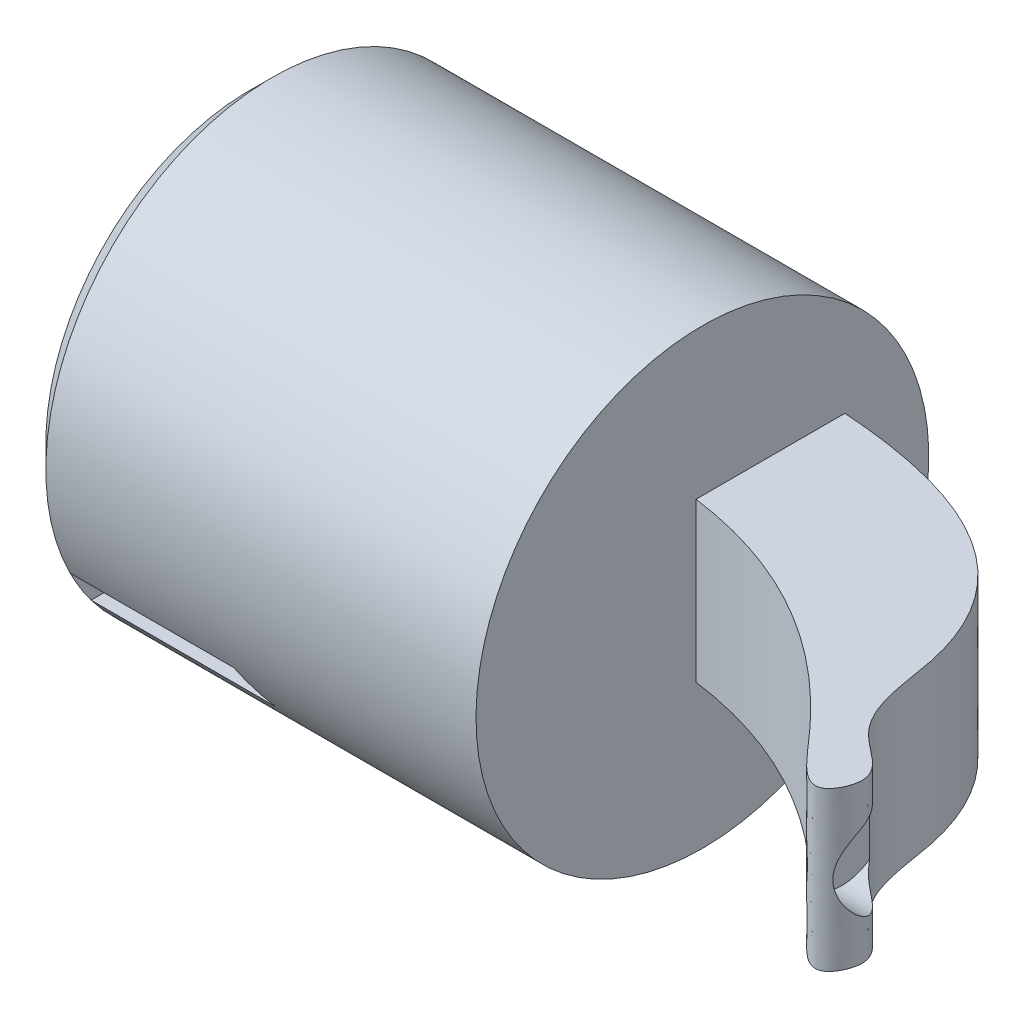
SolidWorks part; units mm, degrees
ref_plane "Front Plane" through (0, 0, 0) normal (0, 0, 1) x (1, 0, 0)
ref_plane "Top Plane" through (0, 0, 0) normal (0, 1, 0) x (1, 0, 0)
ref_plane "Right Plane" through (0, 0, 0) normal (1, 0, 0) x (0, 0, -1)
sketch "Sketch1" plane through (0, 0, 0) normal (1, 0, 0) x (0, 0, -1)
  circle A0 centre (0, 0) radius 10
  dimension "D1" = 20
extrude "Boss-Extrude1" add sketch "Sketch1" against normal blind 20
sketch "Sketch2" plane through (0, 0, 0) normal (0, 1, 0) x (1, 0, 0)
  line L0 (-20, 10) -> (-20, -10) construction
  line L1 (-20, 4.5525) -> (-20, -4.6526)
  spline S0 degree 3 poles (-20, 4.5525) (-5.332, 6.7288) (11.3502, 9.204) (11.7503, -5.3297) (14.9005, -6.7625) (13.6635, -9.4088) (3.0716, 4.2603) (-8.9296, -0.3759) (-20, -4.6526) knots 0 0 0 0 0.428984 0.487895 0.520452 0.537439 0.573313 1 1 1 1
extrude "Boss-Extrude3" add sketch "Sketch2" along normal mid plane 7
fillet "Fillet6" radius 0.1 rebuild error yes
fillet "Fillet7" radius 0.1 rebuild error yes
chamfer "Chamfer1" distance 1 angle 45 1 edges at (-20, 0, -10)
chamfer "Chamfer2" distance 0.5 angle 45 rebuild error yes
chamfer "Chamfer3" distance 1 angle 45 rebuild error yes
sketch "Sketch5" plane through (0, 0, 0) normal (0, 1, 0) x (1, 0, 0)
  line L0 (3.049, 10) -> (1.6255, -4.5314)
  line L1 (0, 10) -> (-19, 10) construction
  line L2 (1.6255, -4.5314) -> (1.6255, -2.5628)
  line L3 (1.6255, -2.5628) -> (0.6261, -1.5633)
  line L4 (0.6261, -1.5633) -> (0.6261, 0)
  line L5 (0.6261, 0) -> (1.6255, 0.7385)
  line L6 (1.6255, 0.7385) -> (1.6255, 2.798)
  line L7 (1.6255, 2.798) -> (1.6842, 3.3967)
  line L8 (1.6842, 3.3967) -> (1.6842, 4.5243)
  line L9 (1.6842, 4.5243) -> (-12.8402, -10)
  line L10 (-19, -10) -> (0, -10) construction
  line L11 (-12.8402, -10) -> (-19, -10)
  line L12 (-19, -10) -> (-19, 10)
  line L13 (-19, 10) -> (3.049, 10)
extrude "Cut-Extrude3" cut sketch "Sketch5" along normal blind 1.5 from offset 6 offset against normal yes
sketch "Sketch6" plane through (0, 0, 0) normal (1, 0, 0) x (0, 0, -1)
  circle A0 centre (-6.3173, 0) radius 2
  point P2 (-6.3173, 0)
  dimension "D1" = 4
extrude "Cut-Extrude4" cut sketch "Sketch6" against normal mid plane 15 from offset 20
